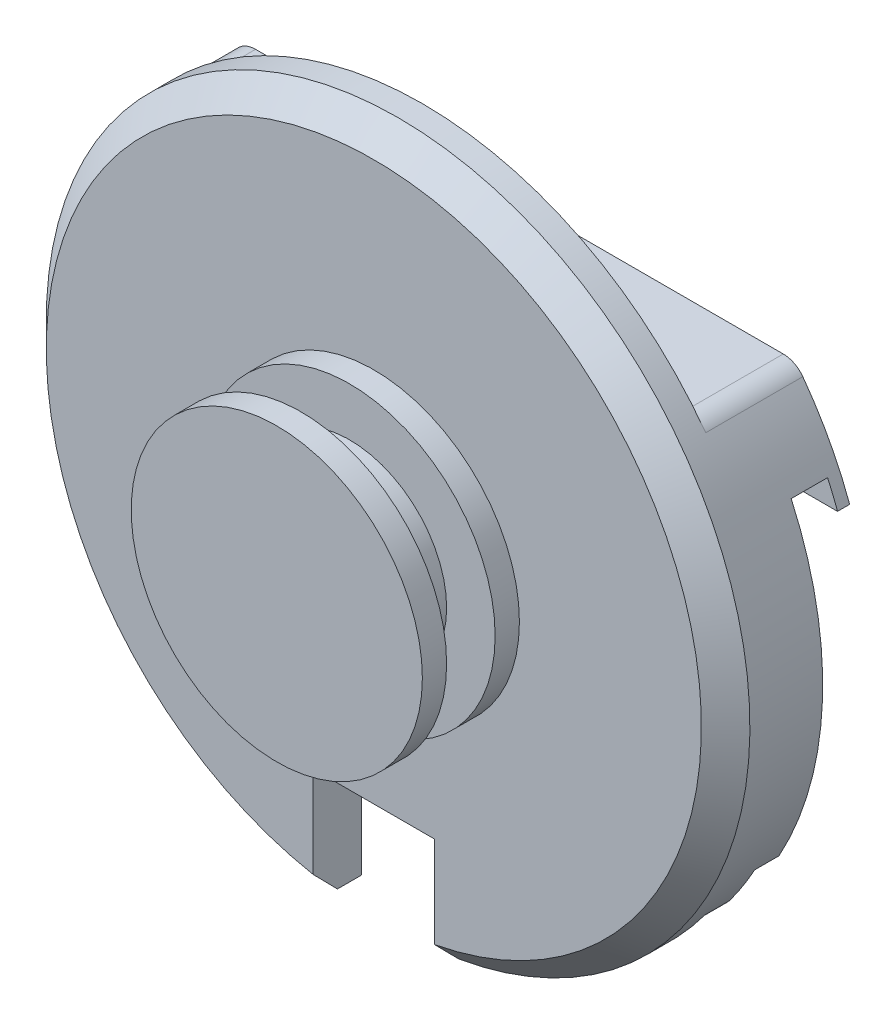
SolidWorks part; units mm, degrees
ref_plane "Front Plane" through (0, 0, 0) normal (0, 0, 1) x (1, 0, 0)
ref_plane "Top Plane" through (0, 0, 0) normal (0, 1, 0) x (1, 0, 0)
ref_plane "Right Plane" through (0, 0, 0) normal (1, 0, 0) x (0, 0, -1)
sketch "Sketch1" plane through (0, 0, 0) normal (0, 0, 1) x (1, 0, 0)
  circle A0 centre (0, 0) radius 14.5
  dimension "D1" = 29
extrude "Extrude1" add sketch "Sketch1" along normal blind 2
chamfer "Chamfer1" distance 1 angle 45 1 edges at (14.5, 0, 2)
sketch "Sketch2" plane through (0, 0, 2) normal (0, 0, 1) x (1, 0, 0)
  circle A0 centre (0, 0) radius 6
  dimension "D1" = 12
extrude "Extrude2" add sketch "Sketch2" along normal blind 1
sketch "Sketch3" plane through (0, 0, 3) normal (0, 0, 1) x (1, 0, 0)
  circle A0 centre (0, 0) radius 4
  dimension "D1" = 8
extrude "Extrude3" add sketch "Sketch3" along normal blind 2
sketch "Sketch4" plane through (0.3898, -0.9593, 5) normal (0, 0, 1) x (1, 0, 0)
  circle A1 centre (-0.3898, 0.9593) radius 6
  circle A2 centre (-0.3898, 0.9593) radius 6
  dimension "D1" = 0
extrude "Extrude4" add sketch "Sketch4" along normal blind 1
sketch "Sketch5" plane through (0, 0, 0) normal (0, 0, -1) x (-1, 0, 0)
  line L0 (-11.3688, 9) -> (11.3688, 9)
  line L1 (-12.6984, -7) -> (12.6984, -7)
  line L2 (0, 0) -> (7.7671, 0) construction
  arc A0 (-11.3688, 9) -> (-12.6984, -7) centre (0, 0) ccw
  circle A1 centre (0, 0) radius 14.5
  arc A2 (12.6984, -7) -> (11.3688, 9) centre (0, 0) ccw
  dimension "D2" = 9
  dimension "D3" = 7
  dimension "D1" = 0
extrude "Extrude5" add sketch "Sketch5" along normal blind 2
sketch "Sketch6" plane through (0, 0, -2) normal (0, 0, -1) x (-1, 0, 0)
  circle A0 centre (0, 0) radius 2
  dimension "D1" = 4
extrude "Cut-Extrude1" cut sketch "Sketch6" against normal blind 7 draft 5
sketch "Sketch7" plane through (0, 0, 0) normal (1, 0, 0) x (0, 0, -1)
  line L0 (2, 9) -> (4, 9)
  line L1 (4, 9) -> (4, 5)
  line L2 (4, 5) -> (3.5, 5)
  line L3 (3.5, 5) -> (3.5, 6)
  line L4 (3.5, 6) -> (2, 6)
  line L5 (2, -7) -> (2, 9) construction
  line L6 (2, 6) -> (2, 9)
  dimension "D1" = 2
  dimension "D2" = 4
  dimension "D3" = 1
  dimension "D4" = 0.5
extrude "Extrude6" add sketch "Sketch7" along normal up to surface and the other way up to surface up to face at (14.5, 0, 1) other way up to face at (14.5, 0, 1)
sketch "Sketch8" plane through (0, 2, 0) normal (-1, 0, 0) x (0, 0, -1)
  line L0 (2, 9) -> (4, 9)
  line L1 (4, 9) -> (4, 5)
  line L2 (4, 5) -> (3.5, 5)
  line L3 (3.5, 5) -> (3.5, 6)
  line L4 (3.5, 6) -> (2, 6)
  line L5 (2, -4) -> (2, 9) construction
  line L6 (2, 6) -> (2, 9)
  line L7 (2, 9) -> (0, 9) construction
extrude "Extrude7" add sketch "Sketch8" along normal mid plane 12
sketch "Sketch9" plane through (0, 0, 0) normal (0, 0, -1) x (-1, 0, 0)
  line L0 (-11.3688, -9) -> (-6.5, -9)
  line L1 (12.6984, -7) -> (-12.6984, -7)
  line L2 (12.6984, -7) -> (-12.6984, -7)
  line L3 (-6.5, -9) -> (-6.5, -10)
  line L4 (-6.5, -10) -> (6.5, -10)
  line L5 (6.5, -10) -> (6.5, -9)
  line L6 (6.5, -9) -> (11.3688, -9)
  line L7 (0, 0) -> (0, -10) construction
  arc A0 (11.3688, -9) -> (12.6984, -7) centre (0, 0) ccw
  arc A1 (-12.6984, -7) -> (12.6984, -7) centre (0, 0) ccw
  arc A2 (-12.6984, -7) -> (-11.3688, -9) centre (0, 0) ccw
  dimension "D2" = 9
  dimension "D3" = 10
  dimension "D4" = 13
  dimension "D1" = 0
extrude "Extrude8" add sketch "Sketch9" along normal blind 1
sketch "Sketch10" plane through (0, 0, -1) normal (0, 0, -1) x (-1, 0, 0)
  line L0 (-5, -8.5) -> (5, -8.5)
  line L1 (0, 0) -> (0, -8.5) construction
  arc A0 (-11.3688, -9) -> (11.3688, -9) centre (0, 0) ccw construction
  dimension "D2" = 6
  dimension "D1" = 10
extrude "Extrude-Thin1" add sketch "Sketch10" along normal blind 8 thin thin type one direction wall 1
sketch "Sketch11" plane through (0, -9.5, 0) normal (0, 1, 0) x (-1, 0, 0)
  line L0 (13.5, 2) -> (-13.5, 2) construction
  line L1 (2.5, 2) -> (-2.5, 2)
  line L3 (2.5, -9) -> (-2.5, -9)
  line L4 (-2.5, -9) -> (-2.5, 2)
  line L5 (2.5, 2) -> (2.5, -9)
  line L6 (0, 0) -> (0, -9) construction
  line L7 (-5, -9) -> (5, -9) construction
  dimension "D1" = 5
extrude "Cut-Extrude3" cut sketch "Sketch11" against normal through all
fillet "Fillet1" radius 1 4 edges at (11.3688, -9, -0.5) (-11.3688, -9, -0.5)
